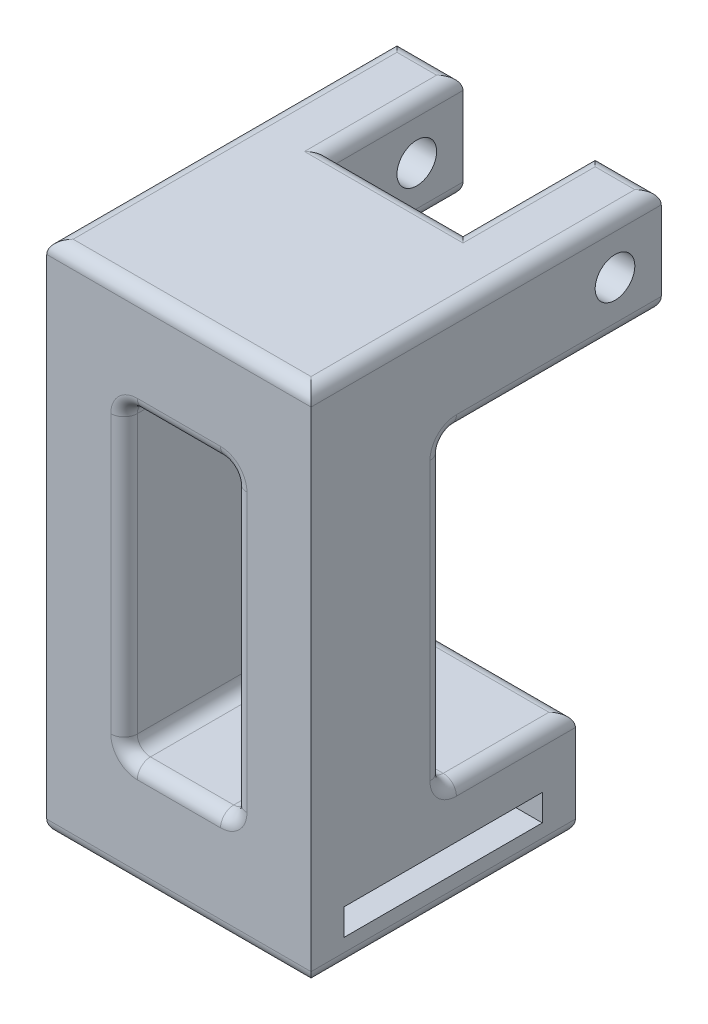
SolidWorks part; units mm, degrees
ref_plane "Alzado" through (0, 0, 0) normal (0, 0, 1) x (1, 0, 0)
ref_plane "Planta" through (0, 0, 0) normal (0, 1, 0) x (1, 0, 0)
ref_plane "Vista lateral" through (0, 0, 0) normal (1, 0, 0) x (0, 0, -1)
sketch "Croquis1" plane through (0, 0, 0) normal (1, 0, 0) x (0, 0, -1)
  line L0 (0, 19.5) -> (0, 11.5) construction
  line L9 (0, 19.5) -> (-28, 19.5) construction
  line L18 (0, 19.5) -> (0, -19.5) construction
  line L19 (0, -19.5) -> (-28, -19.5) construction
  line L20 (-28, 19.5) -> (-28, -19.5)
  line L25 (0, 11.5) -> (-18, 11.5) construction
  line L26 (0, 11.5) -> (0, -11.5) construction
  line L27 (0, -11.5) -> (-18, -11.5) construction
  line L28 (-18, 11.5) -> (-18, -11.5)
  line L29 (0, -11.5) -> (0, -19.5) construction
  line L30 (-1.5, 19.5) -> (-28, 19.5)
  line L31 (-1.5, 19.5) -> (-1.5, 11.5)
  line L32 (-18, 11.5) -> (-1.5, 11.5)
  line L33 (-8, -11.5) -> (-8, -19.5)
  line L34 (-18, -11.5) -> (-8, -11.5)
  line L35 (-28, -19.5) -> (-8, -19.5)
  circle A0 centre (-5, 15.5) radius 1.5
  point P9 (0, 0)
  point P12 (0, 15.5)
  point P13 (-9, -11.5)
  dimension "D6" = 3
  dimension "D1" = 28
  dimension "D2" = 23
  dimension "D3" = 8
  dimension "D4" = 8
  dimension "D5" = 10
  dimension "D7" = 5
  dimension "D8" = 3
  dimension "D9" = 20
extrude "Saliente-Extruir1" add sketch "Croquis1" along normal mid plane 20
sketch "Croquis2" plane through (0, 19.5, 0) normal (0, 1, 0) x (1, 0, 0)
  line L7 (10, -1.5) -> (-10, -1.5) construction
  line L8 (-5, -1.5) -> (5, -1.5)
  line L9 (-5, -1.5) -> (-5, -11.5)
  line L10 (-5, -11.5) -> (5, -11.5)
  line L11 (5, -1.5) -> (5, -11.5)
  point P6 (0, -1.5)
  dimension "D1" = 10
  dimension "D2" = 10
extrude "Cortar-Extruir1" cut sketch "Croquis2" against normal up to surface (8 mm away) up to face at (0, 11.5, 9.75)
sketch "Croquis3" plane through (0, 0, 0) normal (0, 0, 1) x (1, 0, 0)
  line L1 (10, -11.5) -> (-10, -11.5) construction
  line L14 (4.15, -11.5) -> (-4.15, -11.5)
  line L15 (4.15, -11.5) -> (4.15, 11.5)
  line L16 (4.15, 11.5) -> (-4.15, 11.5)
  line L17 (-4.15, -11.5) -> (-4.15, 11.5)
  line L18 (10, 11.5) -> (-10, 11.5) construction
  point P8 (0, 11.5)
  dimension "D1" = 8.3
extrude "Cortar-Extruir3" cut sketch "Croquis3" against normal through all and the other way through all
sketch "Croquis4" plane through (0, 0, 0) normal (1, 0, 0) x (0, 0, -1)
  line L0 (-28, -19.5) -> (-8, -19.5) construction
  line L1 (-25.5, -15.5) -> (-10.5, -15.5)
  line L2 (-25.5, -15.5) -> (-25.5, -17.5)
  line L3 (-25.5, -17.5) -> (-10.5, -17.5)
  line L4 (-10.5, -15.5) -> (-10.5, -17.5)
  line L5 (-25.5, -15.5) -> (-10.5, -17.5) construction
  line L6 (-25.5, -17.5) -> (-10.5, -15.5) construction
  point P0 (-18, -16.5)
  point P7 (-18, -19.5)
  dimension "D1" = 2
  dimension "D2" = 2
  dimension "D3" = 15
extrude "Cortar-Extruir4" cut sketch "Croquis4" against normal through all both and the other way through all
fillet "Redondeo2" radius 1 36 edges at (-10, 0, 18) (-4.15, 0, 28) (4.15, 0, 28) (10, 0, 18) (10, -11.5, 13) (7.075, -11.5, 18) (4.15, -11.5, 23) (0, -11.5, 28) (-4.15, -11.5, 23) (-7.075, -11.5, 18) (-10, -11.5, 13) (0, -11.5, 8) (-7.5, 11.5, 1.5) (-10, 11.5, 9.75) (-7.075, 11.5, 18) (-4.15, 11.5, 23) (0, 11.5, 28) (4.15, 11.5, 23) (7.075, 11.5, 18) (10, 11.5, 9.75) (7.5, 11.5, 1.5) (5, 11.5, 6.5) (0, 11.5, 11.5) (-5, 11.5, 6.5) (5, 19.5, 6.5) (7.5, 19.5, 1.5) (10, 19.5, 14.75) (0, 19.5, 28) (-10, 19.5, 14.75) (-7.5, 19.5, 1.5) (-5, 19.5, 6.5) (0, 19.5, 11.5) (0, -19.5, 28) (10, -19.5, 18) (0, -19.5, 8) (-10, -19.5, 18)
